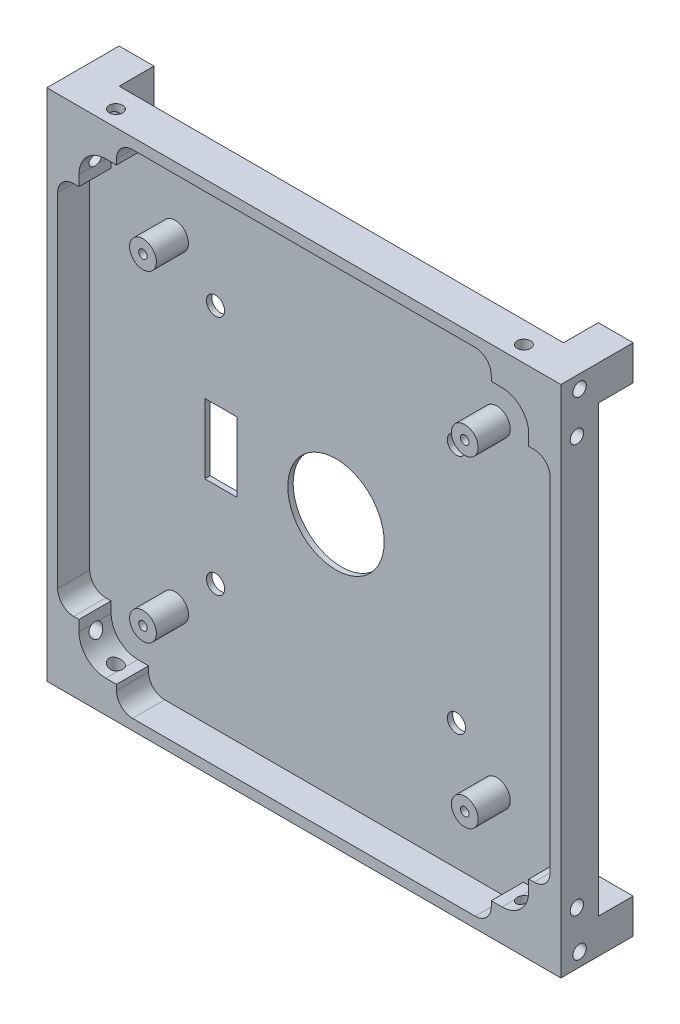
SolidWorks part; units mm, degrees
material "7075-T6 (SN)"
ref_plane "Front Plane" through (0, 0, 0) normal (0, 0, 1) x (1, 0, 0)
ref_plane "Top Plane" through (0, 0, 0) normal (0, 1, 0) x (1, 0, 0)
ref_plane "Right Plane" through (0, 0, 0) normal (1, 0, 0) x (0, 0, -1)
sketch "Sketch1" plane through (0, 0, 0) normal (0, 0, 1) x (1, 0, 0)
  line L1 (48, -48) -> (-48, -48)
  line L2 (48, -48) -> (48, 48)
  line L3 (48, 48) -> (-48, 48)
  line L4 (-48, -48) -> (-48, 48)
  line L5 (48, -48) -> (-48, 48) construction
  line L6 (48, 48) -> (-48, -48) construction
  point P0 (0, 0)
  dimension "D1" = 96
  dimension "D2" = 96
extrude "Boss-Extrude1" add sketch "Sketch1" along normal blind 2
sketch "Sketch2" plane through (0, 0, 2) normal (0, 0, 1) x (1, 0, 0)
  line L0 (48, 48) -> (-48, 48) construction
  line L1 (37, -42) -> (-37, -42)
  line L2 (42, -37) -> (42, 37)
  line L3 (37, 42) -> (-37, 42)
  line L4 (-42, -37) -> (-42, 37)
  line L5 (42, -42) -> (-42, 42) construction
  line L6 (42, 42) -> (-42, -42) construction
  line L7 (48, -48) -> (48, 48) construction
  line L12 (-48, 48) -> (-48, -48)
  line L13 (-48, -48) -> (48, -48)
  line L14 (48, -48) -> (48, 48)
  line L15 (48, 48) -> (-48, 48)
  line L16 (-48, 48) -> (-48, -48)
  line L17 (-48, -48) -> (48, -48)
  line L18 (48, -48) -> (48, 48)
  line L19 (48, 48) -> (-48, 48)
  arc A0 (-37, -42) -> (-42, -37) centre (-37, -37) cw
  arc A1 (37, -42) -> (42, -37) centre (37, -37) ccw
  arc A2 (42, 37) -> (37, 42) centre (37, 37) ccw
  arc A3 (-37, 42) -> (-42, 37) centre (-37, 37) ccw
  point P0 (0, 0)
  dimension "D4" = 5
  dimension "D1" = 6
  dimension "D2" = 6
extrude "Boss-Extrude2" add sketch "Sketch2" along normal blind 5
sketch "Sketch4" plane through (0, 0, 7) normal (0, 0, 1) x (1, 0, 0)
  line L0 (-41.5, 41.5) -> (41.5, -41.5) construction
  line L1 (-41.5, 41.5) -> (41.5, 41.5)
  line L2 (-41.5, 41.5) -> (-41.5, -41.5)
  line L3 (-41.5, -41.5) -> (41.5, -41.5)
  line L4 (41.5, 41.5) -> (41.5, -41.5)
  point P4 (0, 0)
  dimension "D1" = 83
  dimension "D2" = 83
sketch "Sketch3" plane through (0, 0, 0) normal (0, 0, -1) x (-1, 0, 0)
  line L1 (-48, 48) -> (-41.5, 48)
  line L2 (-48, 48) -> (-48, 41.5)
  line L3 (-48, 41.5) -> (-41.5, 41.5)
  line L4 (-41.5, 48) -> (-41.5, 41.5)
  line L5 (48, 48) -> (41.5, 48)
  line L6 (48, 48) -> (48, 41.5)
  line L7 (48, 41.5) -> (41.5, 41.5)
  line L8 (41.5, 48) -> (41.5, 41.5)
  line L9 (-48, -48) -> (-41.5, -48)
  line L10 (-48, -48) -> (-48, -41.5)
  line L11 (-48, -41.5) -> (-41.5, -41.5)
  line L12 (-41.5, -48) -> (-41.5, -41.5)
  line L13 (48, -48) -> (41.5, -48)
  line L14 (48, -48) -> (48, -41.5)
  line L15 (48, -41.5) -> (41.5, -41.5)
  line L16 (41.5, -48) -> (41.5, -41.5)
  dimension "D1" = 6.5
  dimension "D2" = 6.5
  dimension "D3" = 6.5
  dimension "D4" = 6.5
extrude "Boss-Extrude3" add sketch "Sketch3" along normal blind 6.5
sketch "Sketch5" plane through (0, 0, 0) normal (0, 0, -1) x (-1, 0, 0)
  circle A0 centre (0, 0) radius 9
  dimension "D1" = 18
extrude "Cut-Extrude1" cut sketch "Sketch5" against normal blind 10
sketch "Sketch6" plane through (-48, 0, 0) normal (-1, 0, 0) x (0, 0, 1)
  line L0 (-6.5, -45.5) -> (7, -45.5) construction
  line L2 (7, 48) -> (7, -48) construction
  line L3 (-6.5, 45.5) -> (7, 45.5) construction
  line L5 (7, 48) -> (-6.5, 48) construction
  line L6 (7, -48) -> (-6.5, -48) construction
  point P6 (3.5, -45.5)
  point P11 (3.5, 45.5)
  dimension "D1" = 3.5
  dimension "D2" = 3.5
  dimension "D3" = 2.5
  dimension "D4" = 2.5
hole_wizard "M3 Tapped Hole1" positions "3DSketch1" profile "Sketch7" tap size "M3" standard "ISO"
sketch3d "3DSketch1"
  point P0 (-48, 45.5, 3.5)
  point P3 (-48, -45.5, 3.5)
sketch "Sketch7" plane through (-48, 45.5, 3.5) normal (0, 1, 0) x (0, 0, 1)
  line L0 (0, 0) -> (0, 10.2511)
  line L1 (0, 10.2511) -> (1.25, 9.5)
  line L2 (1.25, 9.5) -> (1.25, 0)
  line L5 (1.25, 0) -> (0, 0)
  line L10 (0, 10.2511) -> (-1.25, 9.5) construction
  line L11 (0, -6.35) -> (0, 107.95) construction
  dimension "Tap Drill Dia." = 2.5
  dimension "Tap Drill Depth" = 9.5
  dimension "Drill Angle" = 118
cosmetic thread "Hole Thread1" parameters "D1"=8, "D2"=3
cosmetic thread "Hole Thread2" parameters "D1"=8, "D2"=3
mirror "Mirror1" about plane through (0, 0, 0) normal (1, 0, 0) of "M3 Tapped Hole1"
sketch "Sketch8" plane through (48, 0, 0) normal (1, 0, 0) x (0, 0, -1)
  point P0 (-4, -38.0996)
  point P1 (-4, 38.1004)
hole_wizard "M3 Tapped Hole2" positions "3DSketch2" profile "Sketch10" tap size "M3" standard "ISO"
sketch3d "3DSketch2"
  point P0 (48, 38.1004, 4)
  point P3 (48, -38.0996, 4)
sketch "Sketch10" plane through (48, 38.1004, 4) normal (0, 1, 0) x (0, 0, -1)
  line L0 (0, 0) -> (0, 9.2511)
  line L1 (0, 9.2511) -> (1.25, 8.5)
  line L2 (1.25, 8.5) -> (1.25, 0)
  line L5 (1.25, 0) -> (0, 0)
  line L10 (0, 9.2511) -> (-1.25, 8.5) construction
  line L11 (0, -6.35) -> (0, 107.95) construction
  dimension "Tap Drill Dia." = 2.5
  dimension "Tap Drill Depth" = 8.5
  dimension "Drill Angle" = 118
cosmetic thread "Hole Thread3" parameters "D1"=6, "D2"=3
cosmetic thread "Hole Thread4" parameters "D1"=6, "D2"=3
ref_axis "Axis1" through (0, 0, 2) along (0, 0, -1)
pattern_circular "CirPattern1" count 4 every 90 about axis through (0, 0, 2) along (0, 0, -1) of "M3 Tapped Hole2"
sketch "Sketch11" plane through (0, 0, 7) normal (0, 0, 1) x (1, 0, 0)
  line L0 (-37, -42) -> (37, -42) construction
  line L1 (32, -46) -> (-32, -46)
  line L2 (35, -43) -> (35, -42)
  line L3 (35, -42) -> (-35, -42)
  line L4 (-35, -43) -> (-35, -42)
  line L5 (-48, -48) -> (48, -48) construction
  line L6 (48, -48) -> (48, 48) construction
  line L7 (-48, 48) -> (-48, -48) construction
  line L8 (48, 48) -> (-48, 48) construction
  line L9 (-42, -35) -> (-43, -35)
  line L10 (-42, -35) -> (-42, 35)
  line L11 (-42, 35) -> (-43, 35)
  line L12 (-37, -42) -> (37, -42)
  line L13 (42, -37) -> (42, 37)
  line L14 (37, 42) -> (-37, 42)
  line L15 (-42, 37) -> (-42, -37)
  line L16 (-37, -42) -> (37, -42)
  line L17 (42, -37) -> (42, 37)
  line L18 (37, 42) -> (-37, 42)
  line L19 (-42, 37) -> (-42, -37)
  line L20 (-46, -32) -> (-46, 32)
  arc A0 (-43, 35) -> (-46, 32) centre (-43, 32) ccw
  arc A1 (-43, -35) -> (-46, -32) centre (-43, -32) cw
  arc A2 (-32, -46) -> (-35, -43) centre (-32, -43) cw
  arc A3 (32, -46) -> (35, -43) centre (32, -43) ccw
  arc A4 (-42, -37) -> (-37, -42) centre (-37, -37) ccw
  arc A5 (37, -42) -> (42, -37) centre (37, -37) ccw
  arc A6 (42, 37) -> (37, 42) centre (37, 37) ccw
  arc A7 (-37, 42) -> (-42, 37) centre (-37, 37) ccw
  arc A8 (-42, -37) -> (-37, -42) centre (-37, -37) ccw
  arc A9 (37, -42) -> (42, -37) centre (37, -37) ccw
  arc A10 (42, 37) -> (37, 42) centre (37, 37) ccw
  arc A11 (-37, 42) -> (-42, 37) centre (-37, 37) ccw
  point P10 (-35, -42.5)
  line M21 (37, -42) -> (-37, -42)
  line M23 (-42, -37) -> (-42, 37)
  dimension "D1" = 2
  dimension "D8" = 3
  dimension "D2" = 13
  dimension "D3" = 13
  dimension "D5" = 13
  dimension "D6" = 13
  dimension "D7" = 2
extrude "Cut-Extrude2" cut sketch "Sketch11" against normal up to surface (5 mm away) contours A1 L9 L11 A0 L20 M23 | L1 A3 L2 L4 A2 M21 region at (0, -43.9814, 7) region at (-43.9814, 0, 7) up to face at (9, 0, 2)
pattern_circular "CirPattern2" count 2 every 180 about axis through (0, 0, 2) along (0, 0, -1) of "Cut-Extrude2"
sketch "Sketch12" plane through (0, 0, 2) normal (0, 0, 1) x (1, 0, 0)
  line L20 (-37, -42) -> (-35, -42)
  line L21 (-35, -42) -> (-35, -43)
  line L22 (-32, -46) -> (32, -46)
  line L23 (35, -43) -> (35, -42)
  line L24 (35, -42) -> (37, -42)
  line L25 (42, -37) -> (42, -35)
  line L26 (42, -35) -> (43, -35)
  line L27 (46, -32) -> (46, 32)
  line L28 (43, 35) -> (42, 35)
  line L29 (42, 35) -> (42, 37)
  line L30 (37, 42) -> (35, 42)
  line L31 (35, 42) -> (35, 43)
  line L32 (32, 46) -> (-32, 46)
  line L33 (-35, 43) -> (-35, 42)
  line L34 (-35, 42) -> (-37, 42)
  line L35 (-42, 37) -> (-42, 35)
  line L36 (-42, 35) -> (-43, 35)
  line L37 (-46, 32) -> (-46, -32)
  line L38 (-43, -35) -> (-42, -35)
  line L39 (-42, -35) -> (-42, -37)
  line L40 (-37, -42) -> (-35, -42)
  line L41 (-35, -42) -> (-35, -43)
  line L42 (-32, -46) -> (32, -46)
  line L43 (35, -43) -> (35, -42)
  line L44 (35, -42) -> (37, -42)
  line L45 (42, -37) -> (42, -35)
  line L46 (42, -35) -> (43, -35)
  line L47 (46, -32) -> (46, 32)
  line L48 (43, 35) -> (42, 35)
  line L49 (42, 35) -> (42, 37)
  line L50 (37, 42) -> (35, 42)
  line L51 (35, 42) -> (35, 43)
  line L52 (32, 46) -> (-32, 46)
  line L53 (-35, 43) -> (-35, 42)
  line L54 (-35, 42) -> (-37, 42)
  line L55 (-42, 37) -> (-42, 35)
  line L56 (-42, 35) -> (-43, 35)
  line L57 (-46, 32) -> (-46, -32)
  line L58 (-43, -35) -> (-42, -35)
  line L59 (-42, -35) -> (-42, -37)
  arc A12 (-42, -37) -> (-37, -42) centre (-37, -37) ccw
  arc A13 (-35, -43) -> (-32, -46) centre (-32, -43) ccw
  arc A14 (32, -46) -> (35, -43) centre (32, -43) ccw
  arc A15 (37, -42) -> (42, -37) centre (37, -37) ccw
  arc A16 (43, -35) -> (46, -32) centre (43, -32) ccw
  arc A17 (46, 32) -> (43, 35) centre (43, 32) ccw
  arc A18 (42, 37) -> (37, 42) centre (37, 37) ccw
  arc A19 (35, 43) -> (32, 46) centre (32, 43) ccw
  arc A20 (-32, 46) -> (-35, 43) centre (-32, 43) ccw
  arc A21 (-37, 42) -> (-42, 37) centre (-37, 37) ccw
  arc A22 (-43, 35) -> (-46, 32) centre (-43, 32) ccw
  arc A23 (-46, -32) -> (-43, -35) centre (-43, -32) ccw
  arc A24 (-42, -37) -> (-37, -42) centre (-37, -37) ccw
  arc A25 (-35, -43) -> (-32, -46) centre (-32, -43) ccw
  arc A26 (32, -46) -> (35, -43) centre (32, -43) ccw
  arc A27 (37, -42) -> (42, -37) centre (37, -37) ccw
  arc A28 (43, -35) -> (46, -32) centre (43, -32) ccw
  arc A29 (46, 32) -> (43, 35) centre (43, 32) ccw
  arc A30 (42, 37) -> (37, 42) centre (37, 37) ccw
  arc A31 (35, 43) -> (32, 46) centre (32, 43) ccw
  arc A32 (-32, 46) -> (-35, 43) centre (-32, 43) ccw
  arc A33 (-37, 42) -> (-42, 37) centre (-37, 37) ccw
  arc A34 (-43, 35) -> (-46, 32) centre (-43, 32) ccw
  arc A35 (-46, -32) -> (-43, -35) centre (-43, -32) ccw
  dimension "D1" = 0
extrude "Cut-Extrude3" cut sketch "Sketch12" against normal blind 1
sketch "Sketch13" plane through (0, 0, 7) normal (0, 0, 1) x (1, 0, 0)
  line L4 (48, 48) -> (-48, 48)
  line L5 (-48, 48) -> (-48, -48)
  line L6 (-48, -48) -> (48, -48)
  line L7 (48, -48) -> (48, 48)
  line L8 (48, 48) -> (-48, 48)
  line L9 (-48, 48) -> (-48, -48)
  line L10 (-48, -48) -> (48, -48)
  line L11 (48, -48) -> (48, 48)
  dimension "D1" = 0
extrude "Cut-Extrude4" [suppressed] cut sketch "Sketch13" against normal blind 1
sketch "Sketch14" plane through (0, 0, 0) normal (0, 0, -1) x (-1, 0, 0)
  circle A0 centre (0, 0) radius 20
  text T0 "MSSG       -      EYE-SAT" font "Impact" height 4
  dimension "D1" = 40
sketch "Sketch15" plane through (0, 0, 1) normal (0, 0, 1) x (1, 0, 0)
  line L0 (0, 0) -> (-35.5279, 35.5279) construction
  line L1 (0, 0) -> (-32.9127, -32.9127) construction
  circle A0 centre (0, 0) radius 42.5 construction
  circle A1 centre (-30.052, 30.052) radius 2.5
  point P2 (30.052, 30.052)
  point P6 (30.052, -30.052)
  point P9 (-30.052, -30.052)
  point P10 (-30.052, 30.052)
extrude "Boss-Extrude4" add sketch "Sketch15" along normal blind 6
pattern_circular "CirPattern3" count 4 over 360 about axis through (0, 0, 2) along (0, 0, -1) of "Boss-Extrude4" reverse direction yes
hole_wizard "Tap Drill for M2x0.4 Tap1" positions "3DSketch3" profile "Sketch16" hole size "M2x0.4" standard "ANSI Metric"
sketch3d "3DSketch3"
  line L3 (-30.052, 30.052, 7) -> (-30.052, 30.052, 1) construction
  point P0 (-30.052, 30.052, 7)
  point P17 (-30.052, 30.052, 7)
sketch "Sketch16" plane through (-30.052, 30.052, 7) normal (1, 0, 0) x (0, -1, 0)
  line L0 (0, 0) -> (0, 6.4797)
  line L1 (0, 6.4797) -> (0.8, 5.999)
  line L2 (0.8, 5.999) -> (0.8, 0)
  line L5 (0.8, 0) -> (0, 0)
  line L10 (0, 6.4797) -> (-0.8, 5.999) construction
  line L11 (0, -6.35) -> (0, 107.95) construction
  dimension "Hole Dia." = 1.6
  dimension "Hole Depth" = 5.999
  dimension "Drill Angle" = 118
pattern_circular "CirPattern4" count 4 over 360 about axis through (0, 0, 2) along (0, 0, -1) of "Tap Drill for M2x0.4 Tap1"
sketch "Sketch17" plane through (0, 0, 1) normal (0, 0, 1) x (1, 0, 0)
  line L1 (-18.5, -6.5) -> (-24.5, -6.5)
  line L2 (-18.5, -6.5) -> (-18.5, 6.5)
  line L3 (-18.5, 6.5) -> (-24.5, 6.5)
  line L4 (-24.5, -6.5) -> (-24.5, 6.5)
  line L5 (-18.5, -6.5) -> (-24.5, 6.5) construction
  line L6 (-18.5, 6.5) -> (-24.5, -6.5) construction
  point P0 (-21.5, 0)
  dimension "D1" = 13
  dimension "D2" = 6
  dimension "D3" = 21.5
extrude "Cut-Extrude5" cut sketch "Sketch17" against normal blind 10
hole_wizard "M3 Clearance Hole1" positions "3DSketch4" profile "Sketch18" hole size "M3" standard "ANSI Metric" end condition through all
sketch3d "3DSketch4"
  point P0 (-22.5, -22.5, 1)
sketch "Sketch18" plane through (-22.5, -22.5, 1) normal (1, 0, 0) x (0, -1, 0)
  line L0 (0, 0) -> (0, 7.5)
  line L1 (0, 7.5) -> (1.7, 7.5)
  line L2 (1.7, 7.5) -> (1.7, 0)
  line L5 (1.7, 0) -> (0, 0)
  line L11 (0, -6.35) -> (0, 107.95) construction
  dimension "Thru Hole Dia." = 3.4
  dimension "Thru Hole Depth" = 7.5
pattern_circular "CirPattern5" count 4 over 360 about axis through (0, 0, 2) along (0, 0, -1) of "M3 Clearance Hole1"
equation "\"D2@Sketch1\"=\"D1@Sketch1\""
equation "\"thickness\" = 2"
equation "\"D1@Boss-Extrude1\"=\"thickness\""
equation "\"D2@Sketch2\"=\"D1@Sketch2\""
equation "\"D2@Sketch3\"=\"D1@Sketch3\""
equation "\"D3@Sketch3\"=\"D1@Sketch3\""
equation "\"D4@Sketch3\"=\"D1@Sketch3\""
equation "\"D2@Sketch4\"=\"D1@Sketch4\""
equation "\"D2@Sketch6\"=\"D1@Sketch6\""
equation "\"D4@Sketch6\"=\"D3@Sketch6\""
equation "\"D3@Sketch11\"=\"D2@Sketch11\""
equation "\"D5@Sketch11\"=\"D2@Sketch11\""
equation "\"D6@Sketch11\"=\"D2@Sketch11\""
equation "\"D7@Sketch11\"=\"D1@Sketch11\""
